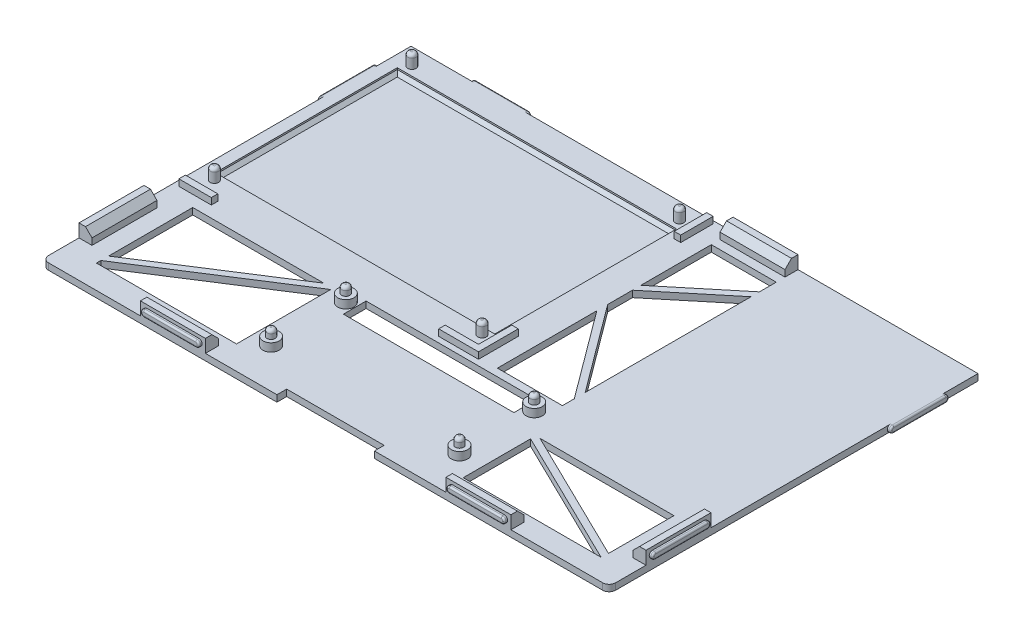
SolidWorks part; units mm, degrees
ref_plane "前基準面" through (0, 0, 0) normal (0, 0, 1) x (1, 0, 0)
ref_plane "上基準面" through (0, 0, 0) normal (0, 1, 0) x (1, 0, 0)
ref_plane "右基準面" through (0, 0, 0) normal (1, 0, 0) x (0, 0, -1)
sketch "草圖1" plane through (0, 0, 0) normal (0, 1, 0) x (1, 0, 0)
  line L0 (0, 56.775) -> (0, -56.775) construction
  line L1 (-87.275, 56.775) -> (87.275, 56.775)
  line L2 (-87.275, 56.775) -> (-87.275, -56.775)
  line L3 (-87.275, -56.775) -> (87.275, -56.775)
  line L4 (87.275, 56.775) -> (87.275, -56.775)
  line L5 (-87.275, 56.775) -> (87.275, -56.775) construction
  line L6 (-87.275, -56.775) -> (87.275, 56.775) construction
  line L7 (-87.275, 0) -> (87.275, 0) construction
  point P0 (0, 0)
  dimension "D1" = 174.55
  dimension "D2" = 113.55
extrude "填料-伸長1" add sketch "草圖1" along normal blind 2
sketch "草圖2" plane through (0, 2, 0) normal (0, 1, 0) x (1, 0, 0)
  line L1 (-85.66, 55.93) -> (4.34, 55.93)
  line L2 (-85.66, 55.93) -> (-85.66, -14.07)
  line L3 (-85.66, -14.07) -> (4.34, -14.07)
  line L4 (4.34, 55.93) -> (4.34, -14.07)
  line L5 (-85.66, 55.93) -> (4.34, -14.07) construction
  line L6 (-85.66, -14.07) -> (4.34, 55.93) construction
  line L8 (-40.66, 55.93) -> (-40.66, -14.07) construction
  line L9 (-85.66, 20.93) -> (4.34, 20.93) construction
  line L10 (0, 56.775) -> (0, -56.775) construction
  line L11 (-87.275, 0) -> (87.275, 0) construction
  point P0 (-40.66, 20.93)
  dimension "D1" = 90
  dimension "D2" = 70
  dimension "D3" = 40.66
  dimension "D4" = 20.93
sketch "草圖3" plane through (0, 2, 0) normal (0, 1, 0) x (1, 0, 0)
  line L0 (4.34, 55.93) -> (4.34, -14.07) construction
  line L1 (4.59, 55.93) -> (6.59, 55.93)
  line L2 (4.59, 55.93) -> (4.59, 45.93)
  line L3 (4.59, 45.93) -> (6.59, 45.93)
  line L4 (6.59, 55.93) -> (6.59, 45.93)
  line L5 (-85.66, -14.07) -> (4.34, -14.07) construction
  line L7 (4.59, -14.07) -> (4.59, -4.07)
  line L8 (4.59, -4.07) -> (6.59, -4.07)
  line L9 (6.59, -14.07) -> (6.59, -4.07)
  line L10 (6.59, -16.32) -> (-5.66, -16.32)
  line L11 (6.59, -16.32) -> (6.59, -15.07)
  line L12 (4.59, -14.32) -> (-5.66, -14.32)
  line L13 (-5.66, -16.32) -> (-5.66, -14.32)
  line L14 (4.34, -14.32) -> (4.34, -16.32) construction
  line L15 (4.59, -14.07) -> (4.59, -14.32)
  line L16 (6.59, -14.07) -> (6.59, -15.07)
  line L18 (-85.66, -16.32) -> (-75.66, -16.32)
  line L19 (-85.66, -16.32) -> (-85.66, -14.32)
  line L20 (-85.66, -14.32) -> (-75.66, -14.32)
  line L21 (-75.66, -16.32) -> (-75.66, -14.32)
  dimension "D1" = 2
  dimension "D2" = 10
  dimension "D3" = 0.25
  dimension "D4" = 2
  dimension "D5" = 2
  dimension "D6" = 2
  dimension "D8" = 0.25
  dimension "D9" = 10
  dimension "D11" = 10
extrude "填料-伸長2" add sketch "草圖3" along normal blind 2
sketch "草圖4" plane through (0, 2, 0) normal (0, 1, 0) x (1, 0, 0)
  line L1 (-85.66, 55.93) -> (4.34, 55.93) construction
  line L2 (4.34, 55.93) -> (4.34, -14.07) construction
  line L3 (-85.66, -14.07) -> (4.34, -14.07) construction
  line L4 (-40.66, 55.93) -> (-40.66, -14.07) construction
  circle A0 centre (0.54, 51.63) radius 1.3
  circle A1 centre (0.54, -9.17) radius 1.3
  circle A2 centre (-81.86, -9.17) radius 1.3
  circle A3 centre (-81.86, 51.63) radius 1.3
  dimension "D1" = 2.6
  dimension "D2" = 3.8
  dimension "D3" = 4.3
  dimension "D4" = 4.9
extrude "填料-伸長3" add sketch "草圖4" along normal blind 4
fillet "圓角2" radius 1 4 edges at (-81.86, 6, -52.93) (-81.86, 6, 7.87) (0.54, 6, 10.47) (0.54, 6, -50.33)
sketch "草圖6" plane through (0, 2, 0) normal (0, 1, 0) x (1, 0, 0)
  line L1 (35.1797, 56.0179) -> (85.1797, 56.0179)
  line L2 (35.1797, 56.0179) -> (35.1797, -24.9821)
  line L3 (35.1797, -24.9821) -> (85.1797, -24.9821)
  line L4 (85.1797, 56.0179) -> (85.1797, -24.9821)
  line L5 (35.1797, 56.0179) -> (85.1797, -24.9821) construction
  line L6 (35.1797, -24.9821) -> (85.1797, 56.0179) construction
  point P0 (60.1797, 15.5179)
  dimension "D1" = 81
  dimension "D2" = 50
sketch "草圖5" plane through (0, 2, 0) normal (0, 1, 0) x (1, 0, 0)
  line L0 (-85.66, 55.93) -> (4.34, -14.07) construction
  line L1 (-83.66, 48.93) -> (2.34, 48.93)
  line L2 (-83.66, 48.93) -> (-83.66, -7.07)
  line L3 (-83.66, -7.07) -> (2.34, -7.07)
  line L4 (2.34, 48.93) -> (2.34, -7.07)
  line L5 (-83.66, 48.93) -> (2.34, -7.07) construction
  line L6 (-83.66, -7.07) -> (2.34, 48.93) construction
  line L7 (-85.66, 55.93) -> (4.34, 55.93) construction
  line L8 (-85.66, 55.93) -> (-85.66, -14.07) construction
  point P0 (-40.66, 20.93)
  dimension "D1" = 7
  dimension "D2" = 2
extrude "除料-伸長1" cut sketch "草圖5" against normal blind 1.5
sketch "草圖7" plane through (0, 2, 0) normal (0, 1, 0) x (1, 0, 0)
  line L0 (0, 56.775) -> (0, -56.775) construction
  line L1 (-32.5, -18.075) -> (32.5, -18.075)
  line L2 (-32.5, -18.075) -> (-32.5, -48.275)
  line L3 (-32.5, -48.275) -> (32.5, -48.275)
  line L4 (32.5, -18.075) -> (32.5, -48.275)
  line L5 (-32.5, -18.075) -> (32.5, -48.275) construction
  line L6 (-32.5, -48.275) -> (32.5, -18.075) construction
  line L7 (-87.275, -56.775) -> (87.275, -56.775) construction
  point P0 (0, -33.175)
  point P5 (32.5, -33.175)
  dimension "D1" = 65
  dimension "D2" = 30.2
  dimension "D3" = 8.5
sketch "草圖8" plane through (0, 2, 0) normal (0, 1, 0) x (1, 0, 0)
  line L0 (-32.5, -18.075) -> (32.5, -18.075) construction
  line L1 (32.5, -18.075) -> (32.5, -48.275) construction
  line L2 (-32.5, -48.275) -> (32.5, -48.275) construction
  line L3 (0, -18.075) -> (0, -48.275) construction
  circle A0 centre (29, -21.575) radius 2.5
  circle A1 centre (29, -21.575) radius 1.25
  circle A2 centre (29, -44.575) radius 2.5
  circle A3 centre (29, -44.575) radius 1.25
  circle A4 centre (-29, -44.575) radius 1.25
  circle A5 centre (-29, -44.575) radius 2.5
  circle A6 centre (-29, -21.575) radius 1.25
  circle A7 centre (-29, -21.575) radius 2.5
  dimension "D1" = 5
  dimension "D4" = 2.5
  dimension "D2" = 3.5
  dimension "D3" = 3.5
  dimension "D5" = 3.7
extrude "填料-伸長4" add sketch "草圖8" along normal blind 2.5 contours A6 | A7 A6 | A5 A4 | A4 | A0 A1 | A1 | A2 A3 | A3 region at (26.5707, 2, 21.575) region at (29, 2, 21.575) region at (26.5707, 2, 44.575) region at (29, 2, 44.575) region at (-29, 2, 44.575) region at (-31.4293, 2, 44.575) region at (-29, 2, 21.575) region at (-31.4293, 2, 21.575)
extrude "填料-伸長5" add sketch "草圖8<3>" along normal blind 5 contours A6 | A4 | A3 | A1 region at (29, 2, 21.575) region at (29, 2, 44.575) region at (-29, 2, 44.575) region at (-29, 2, 21.575)
sketch "草圖8<3>" plane through (0, 2, 0) normal (0, 1, 0) x (1, 0, 0) same geometry as "草圖8"
fillet "圓角3" radius 1 4 edges at (-29, 7, 45.825) (29, 7, 45.825) (29, 7, 22.825) (-29, 7, 22.825)
sketch "草圖9" plane through (0, 2, 0) normal (0, 1, 0) x (1, 0, 0)
  line L0 (0, 56.775) -> (0, -56.775) construction
  line L1 (-26.25, -18.075) -> (26.25, -18.075)
  line L2 (-26.25, -18.075) -> (-26.25, -25.075)
  line L3 (-26.25, -25.075) -> (26.25, -25.075)
  line L4 (26.25, -18.075) -> (26.25, -25.075)
  line L5 (-26.25, -18.075) -> (26.25, -25.075) construction
  line L6 (-26.25, -25.075) -> (26.25, -18.075) construction
  line L7 (-32.5, -18.075) -> (32.5, -18.075) construction
  line L8 (-87.275, -56.775) -> (87.275, -56.775) construction
  line L9 (-15, -53.775) -> (15, -53.775)
  line L10 (-15, -53.775) -> (-15, -56.775)
  line L11 (-15, -56.775) -> (15, -56.775)
  line L12 (15, -53.775) -> (15, -56.775)
  line L13 (-15, -53.775) -> (15, -56.775) construction
  line L14 (-15, -56.775) -> (15, -53.775) construction
  point P0 (0, -21.575)
  point P9 (0, -55.275)
  point P16 (0, -21.575)
  dimension "D1" = 7
  dimension "D2" = 3
  dimension "D3" = 30
  dimension "D4" = 52.5
extrude "除料-伸長2" cut sketch "草圖9" against normal blind 2
sketch "草圖10" plane through (0, 2, 0) normal (0, 1, 0) x (1, 0, 0)
  line L0 (-87.275, 56.775) -> (87.275, 56.775) construction
  line L1 (11.8547, 56.775) -> (31.8547, 56.775)
  line L2 (11.8547, 56.775) -> (11.8547, 52.775)
  line L3 (11.8547, 52.775) -> (31.8547, 52.775)
  line L4 (31.8547, 56.775) -> (31.8547, 52.775)
  line L5 (0, 56.775) -> (0, -56.775) construction
  line L10 (87.275, 56.775) -> (87.275, -56.775) construction
  line L11 (87.275, -25.438) -> (83.275, -25.438)
  line L12 (87.275, -25.438) -> (87.275, -45.438)
  line L13 (87.275, -45.438) -> (83.275, -45.438)
  line L14 (83.275, -25.438) -> (83.275, -45.438)
  line L15 (-87.275, -56.775) -> (87.275, -56.775) construction
  line L16 (37.0319, -56.775) -> (57.0319, -56.775)
  line L17 (37.0319, -56.775) -> (37.0319, -52.775)
  line L18 (37.0319, -52.775) -> (57.0319, -52.775)
  line L19 (57.0319, -56.775) -> (57.0319, -52.775)
  line L20 (-57.0319, -56.775) -> (-57.0319, -52.775)
  line L21 (-37.0319, -52.775) -> (-57.0319, -52.775)
  line L22 (-37.0319, -56.775) -> (-37.0319, -52.775)
  line L23 (-37.0319, -56.775) -> (-57.0319, -56.775)
  line L29 (-83.275, -25.438) -> (-83.275, -45.438)
  line L30 (-87.275, -45.438) -> (-83.275, -45.438)
  line L31 (-87.275, -25.438) -> (-87.275, -45.438)
  line L32 (-87.275, -25.438) -> (-83.275, -25.438)
  dimension "D1" = 4
  dimension "D2" = 20
  dimension "D5" = 20
  dimension "D6" = 4
  dimension "D7" = 20
  dimension "D8" = 4
  dimension "D10" = 82.213
extrude "填料-伸長6" add sketch "草圖10" along normal blind 4
sketch "草圖11" plane through (0, 2, 0) normal (0, 1, 0) x (1, 0, 0)
  line L0 (-77.8796, -45.7226) -> (-37.4971, -19.8239)
  line L1 (-77.8796, -49.4672) -> (-34.7645, -49.4672)
  line L2 (-77.8796, -49.4672) -> (-77.8796, -48.0986)
  line L3 (-77.8796, -19.8239) -> (-37.4971, -19.8239)
  line L4 (-34.7645, -49.4672) -> (-34.7645, -20.4474)
  line L5 (-77.8796, -48.0986) -> (-34.7645, -20.4474)
  line L6 (-77.8796, -45.7226) -> (-77.8796, -19.8239)
  line L7 (31.8547, 44.9175) -> (11.8547, 28.4103)
  line L8 (11.8547, 50.0907) -> (31.8547, 50.0907)
  line L9 (11.8547, 50.0907) -> (11.8547, 28.4103)
  line L10 (11.8547, -15.7529) -> (31.8547, -15.7529)
  line L11 (31.8547, 50.0907) -> (31.8547, 44.9175)
  line L13 (11.8547, 25.8171) -> (31.8547, 42.3243)
  line L14 (11.8547, 18.1985) -> (31.8547, -8.7367)
  line L15 (11.8547, 14.8436) -> (31.8547, -12.0916)
  line L16 (31.8547, 42.3243) -> (31.8547, -8.7367)
  line L17 (11.8547, 25.8171) -> (11.8547, 18.1985)
  line L18 (11.8547, 14.8436) -> (11.8547, -15.7529)
  line L19 (31.8547, -12.0916) -> (31.8547, -15.7529)
  line L20 (78.3594, -48.0628) -> (37.1158, -27.9151)
  line L21 (37.1158, -27.9151) -> (78.3594, -27.9151)
  line L22 (35.8042, -29.5002) -> (35.8042, -50.2291)
  line L23 (35.8042, -50.2291) -> (78.2374, -50.2291)
  line L24 (78.3594, -27.9151) -> (78.3594, -48.0628)
  line L25 (35.8042, -29.5002) -> (78.2374, -50.2291)
  dimension "D1" = 2
  dimension "D2" = 2
  dimension "D3" = 2
  dimension "D4" = 2
extrude "除料-伸長3" cut sketch "草圖11" against normal through all
fillet "圓角1" radius 2 2 edges at (-87.275, 1, 56.775) (87.275, 1, 56.775)
chamfer "導角1" distance 2 angle 45 5 edges at (83.275, 6, 35.438) (47.0319, 6, 52.775) (-47.0319, 6, 52.775) (21.8547, 6, -52.775) (-83.275, 6, 35.438)
sketch "草圖13" plane through (87.275, 0, 0) normal (1, 0, 0) x (0, 0, -1)
  line L0 (-43.438, 4) -> (-27.438, 4) construction
  line L1 (-43.438, 5) -> (-27.438, 5)
  line L2 (-43.438, 3) -> (-27.438, 3)
  line L4 (-45.438, 4) -> (-25.438, 4) construction
  line L5 (-45.438, 6) -> (-45.438, 2) construction
  arc A0 (-43.438, 5) -> (-43.438, 3) centre (-43.438, 4) ccw
  arc A1 (-27.438, 3) -> (-27.438, 5) centre (-27.438, 4) ccw
  point P2 (-35.438, 4)
  point P16 (-35.438, 4)
  dimension "D1" = 2
  dimension "D2" = 16
extrude "填料-伸長8" add sketch "草圖13" along normal blind 1
sketch "草圖14" plane through (0, 0, -56.775) normal (0, 0, -1) x (-1, 0, 0)
  line L0 (-31.8547, 4) -> (-11.8547, 4) construction
  line L1 (-31.8547, 6) -> (-31.8547, 2) construction
  line L2 (-29.8547, 4) -> (-13.8547, 4) construction
  line L3 (-29.8547, 5) -> (-13.8547, 5)
  line L4 (-29.8547, 3) -> (-13.8547, 3)
  arc A0 (-29.8547, 5) -> (-29.8547, 3) centre (-29.8547, 4) ccw
  arc A1 (-13.8547, 3) -> (-13.8547, 5) centre (-13.8547, 4) ccw
  point P7 (-21.8547, 4)
  point P13 (-21.8547, 4)
  dimension "D1" = 16
  dimension "D2" = 2
extrude "填料-伸長9" add sketch "草圖14" along normal blind 1
sketch "草圖15" plane through (0, 0, 56.775) normal (0, 0, 1) x (1, 0, 0)
  line L0 (-57.0319, 4) -> (-37.0319, 4) construction
  line L1 (-57.0319, 6) -> (-57.0319, 2) construction
  line L2 (-37.0319, 6) -> (-37.0319, 2) construction
  line L3 (-55.0319, 4) -> (-39.0319, 4) construction
  line L4 (-55.0319, 5) -> (-39.0319, 5)
  line L5 (-55.0319, 3) -> (-39.0319, 3)
  line L6 (0, 2) -> (0, 0) construction
  line L7 (55.0319, 4) -> (39.0319, 4) construction
  line L8 (55.0319, 5) -> (39.0319, 5)
  line L9 (55.0319, 3) -> (39.0319, 3)
  arc A0 (-55.0319, 5) -> (-55.0319, 3) centre (-55.0319, 4) ccw
  arc A1 (-39.0319, 3) -> (-39.0319, 5) centre (-39.0319, 4) ccw
  arc A2 (55.0319, 5) -> (55.0319, 3) centre (55.0319, 4) cw
  arc A3 (39.0319, 3) -> (39.0319, 5) centre (39.0319, 4) cw
  point P8 (-47.0319, 4)
  point P16 (47.0319, 4)
  dimension "D1" = 16
  dimension "D2" = 2
extrude "填料-伸長11" add sketch "草圖15" along normal blind 1
sketch "草圖16" plane through (-87.275, 0, 0) normal (-1, 0, 0) x (0, 0, 1)
  line L0 (25.438, 6) -> (45.438, 6) construction
  line L3 (27.438, 4) -> (43.438, 4) construction
  line L4 (27.438, 5) -> (43.438, 5)
  line L5 (27.438, 3) -> (43.438, 3)
  arc A0 (27.438, 5) -> (27.438, 3) centre (27.438, 4) ccw
  arc A1 (43.438, 3) -> (43.438, 5) centre (43.438, 4) ccw
  point P3 (35.438, 6)
  point P8 (35.438, 4)
  dimension "D1" = 16
  dimension "D2" = 2
extrude "填料-伸長12" add sketch "草圖16" along normal blind 1
ref_plane "Plane7" through (0, 0, 0) normal (-1, 0, 0) x (0, 0, 1)
sketch "Sketch1" plane through (0, 0, -56.775) normal (0, 0, -1) x (-1, 0, 0)
  line L0 (68.15, 1) -> (52.15, 1) construction
  line L1 (68.15, 0) -> (52.15, 0)
  line L2 (68.15, 2) -> (52.15, 2)
  line L3 (87.275, 2) -> (87.275, 0) construction
  arc A0 (68.15, 0) -> (68.15, 2) centre (68.15, 1) ccw
  arc A1 (52.15, 2) -> (52.15, 0) centre (52.15, 1) ccw
  point P2 (60.15, 1)
  point P7 (87.275, 1)
  dimension "D1" = 16
  dimension "D2" = 2
  dimension "D3" = 60.15
extrude "Boss-Extrude1" add sketch "Sketch1" along normal blind 1
sketch "Sketch2" plane through (87.275, 0, 0) normal (1, 0, 0) x (0, 0, -1)
  line L0 (29.84, 1) -> (45.84, 1) construction
  line L1 (29.84, 2) -> (45.84, 2)
  line L2 (29.84, 0) -> (45.84, 0)
  line L3 (56.775, 0) -> (56.775, 2) construction
  arc A0 (29.84, 2) -> (29.84, 0) centre (29.84, 1) ccw
  arc A1 (45.84, 0) -> (45.84, 2) centre (45.84, 1) ccw
  point P2 (37.84, 1)
  point P7 (56.775, 1)
  dimension "D1" = 16
  dimension "D2" = 2
  dimension "D3" = 37.84
extrude "Boss-Extrude2" add sketch "Sketch2" along normal blind 1
mirror "Mirror1" about plane through (0, 0, 0) normal (-1, 0, 0) of "Boss-Extrude2"
fillet "圓角4" radius 0.5 32 edges at (12.8547, 4, -57.775) (21.8547, 3, -57.775) (30.8547, 4, -57.775) (88.275, 4, 26.438) (88.275, 3, 35.438) (88.275, 4, 44.438) (56.0319, 4, 57.775) (47.0319, 3, 57.775) (38.0319, 4, 57.775) (-88.275, 4, 44.438) (-88.275, 3, 35.438) (-88.275, 4, 26.438) (-38.0319, 4, 57.775) (-47.0319, 3, 57.775) (-56.0319, 4, 57.775) (21.8547, 5, -57.775) (88.275, 5, 35.438) (47.0319, 5, 57.775) (-88.275, 5, 35.438) (-47.0319, 5, 57.775) (-88.275, 1, -46.84) (-88.275, 0, -37.84) (-88.275, 1, -28.84) (88.275, 1, -46.84) (88.275, 0, -37.84) (88.275, 1, -28.84) (-69.15, 1, -57.775) (-60.15, 0, -57.775) (-51.15, 1, -57.775) (-88.275, 2, -37.84) (88.275, 2, -37.84) (-60.15, 2, -57.775)
chamfer "Chamfer1" distance 1 angle 45 4 edges at (2.34, 0.5, -20.93) (-40.66, 0.5, 7.07) (-83.66, 0.5, -20.93) (-40.66, 0.5, -48.93)
